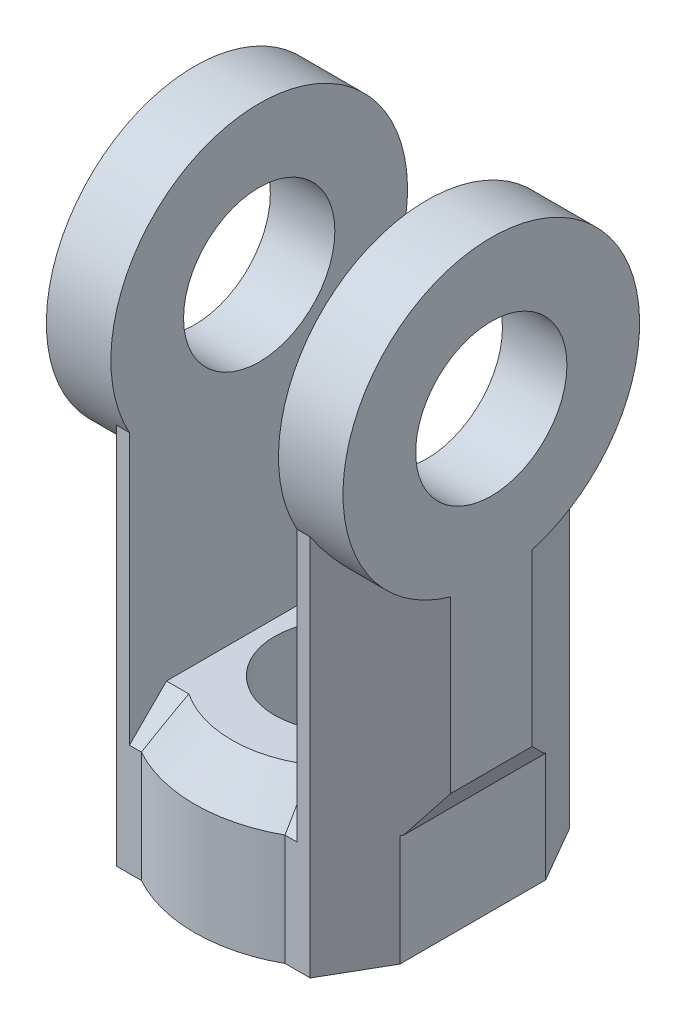
SolidWorks part; units mm, degrees
note: The reader was unsure of these and kept them because the rebuilt part matched: shared geometry of "Sketch6<2>".
ref_plane "Front" through (0, 0, 0) normal (0, 0, 1) x (1, 0, 0)
ref_plane "Top" through (0, 0, 0) normal (0, 1, 0) x (1, 0, 0)
ref_plane "Right" through (0, 0, 0) normal (1, 0, 0) x (0, 0, -1)
sketch "Sketch1" plane through (0, 0, 0) normal (0, 1, 0) x (1, 0, 0)
  line L0 (-25.4, -22.225) -> (-12.2967, -22.225)
  line L2 (-12.2967, 22.225) -> (-25.4, 22.225)
  line L3 (-25.4, 22.225) -> (-25.4, -22.225)
  line L5 (12.2967, 22.225) -> (25.4, 22.225)
  line L6 (25.4, 22.225) -> (25.4, -22.225)
  line L7 (25.4, -22.225) -> (12.2967, -22.225)
  arc A0 (12.2967, 22.225) -> (-12.2967, 22.225) centre (0, 0) ccw
  arc A1 (-12.2967, -22.225) -> (12.2967, -22.225) centre (0, 0) ccw
  dimension "D1" = 25.4
  dimension "D2" = 44.45
  dimension "D3" = 22.225
extrude "Boss-Extrude1" add sketch "Sketch1" along normal blind 25.4
sketch "Sketch2" plane through (0, 25.4, 0) normal (0, 1, 0) x (1, 0, 0)
  line L0 (-25.4, -22.225) -> (-25.4, 22.225)
  line L1 (-25.4, 22.225) -> (-14.351, 22.225)
  line L2 (-14.351, 22.225) -> (-14.351, -22.225)
  line L3 (-14.351, -22.225) -> (-25.4, -22.225)
  line L4 (25.4, -22.225) -> (14.351, -22.225)
  line L5 (14.351, -22.225) -> (14.351, 22.225)
  line L6 (14.351, 22.225) -> (25.4, 22.225)
  line L7 (25.4, 22.225) -> (25.4, -22.225)
  dimension "D1" = 28.702
extrude "Boss-Extrude2" add sketch "Sketch2" along normal blind 52.324
chamfer "Chamfer1" distance 6.35 angle 45 6 edges at (-13.3239, 25.4, -22.225) (13.3239, 25.4, -22.225) (0, 25.4, -25.4) (13.3239, 25.4, 22.225) (-13.3239, 25.4, 22.225) (0, 25.4, 25.4)
hole_wizard "1-12 Tapped Hole1" positions "Sketch3" profile "Sketch4" tap size "1-12" standard "ANSI Inch" end condition through all
sketch "Sketch3" plane through (0, 0, 0) normal (0, -1, 0) x (-1, 0, 0)
  point P0 (0, 0)
sketch "Sketch4" plane through (0, 0, 0) normal (1, 0, 0) x (0, 0, -1)
  line L0 (0, 0) -> (0, 77.724)
  line L1 (0, 77.724) -> (11.7081, 77.724)
  line L2 (11.7081, 77.724) -> (11.7081, 0)
  line L5 (11.7081, 0) -> (0, 0)
  line L11 (0, -6.35) -> (0, 107.95) construction
  dimension "Thru Tap Drill Dia." = 23.4163
  dimension "Thru Tap Drill Depth" = 77.724
cosmetic thread "Hole Thread1" parameters "D2"=25.4
chamfer "Chamfer2" distance 15.24 angle 30 4 edges at (25.4, 38.862, -22.225) (-25.4, 38.862, 22.225) (25.4, 38.862, 22.225) (-25.4, 38.862, -22.225)
sketch "Sketch5" plane through (0, 0, 0) normal (0, -1, 0) x (1, 0, 0)
  line L0 (-22.225, 20.8076) -> (-22.225, -24.6923)
  line L1 (-22.225, -24.6923) -> (-53.5287, -24.6923)
  line L2 (-53.5287, -24.6923) -> (-53.5287, 20.8076)
  line L3 (-53.5287, 20.8076) -> (-22.225, 20.8076)
  line L4 (0, 0) -> (0, 42.3003) construction
  line L5 (53.5287, 20.8076) -> (22.225, 20.8076)
  line L6 (53.5287, -24.6923) -> (53.5287, 20.8076)
  line L7 (22.225, -24.6923) -> (53.5287, -24.6923)
  line L8 (22.225, 20.8076) -> (22.225, -24.6923)
  dimension "D1" = 22.225
extrude "Cut-Extrude1" cut sketch "Sketch5" against normal blind 19.05
sketch "Sketch6" plane through (25.4, 0, 0) normal (1, 0, 0) x (0, 0, -1)
  line L0 (-6.985, 77.724) -> (6.985, 77.724) construction
  circle A0 centre (0, 77.724) radius 25.4
  dimension "D1" = 50.8
extrude "Boss-Extrude3" add sketch "Sketch6" against normal up to surface (11.049 mm away) up to face at (14.351, 40.7247, 0)
extrude "Boss-Extrude4" add sketch "Sketch6<2>" along normal up to surface (11.049 mm away) from offset 50.8
sketch "Sketch6<2>" plane through (25.4, 0, 0) normal (1, 0, 0) x (0, 0, -1) same geometry as "Sketch6"
sketch "Sketch7" plane through (25.4, 0, 0) normal (1, 0, 0) x (0, 0, -1)
  circle A0 centre (0, 77.724) radius 12.954
  dimension "D1" = 25.908
extrude "Cut-Extrude2" cut sketch "Sketch7" against normal through all
chamfer "Chamfer4" distance 5.08 angle 30 2 edges at (-25.4, 19.05, 0) (25.4, 19.05, 0)
